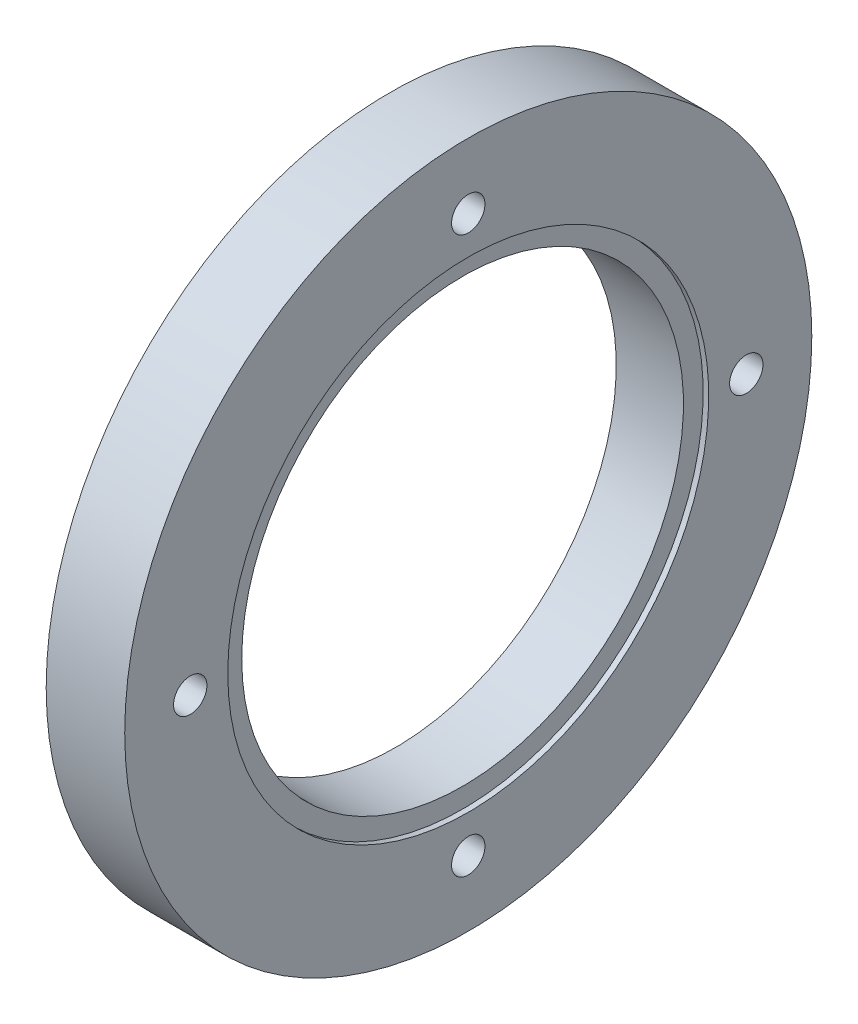
SolidWorks part; units mm, degrees
ref_plane "Front Plane" through (0, 0, 0) normal (0, 0, 1) x (1, 0, 0)
ref_plane "Top Plane" through (0, 0, 0) normal (0, 1, 0) x (1, 0, 0)
ref_plane "Right Plane" through (0, 0, 0) normal (1, 0, 0) x (0, 0, -1)
sketch "Sketch1" plane through (0, 0, 0) normal (0, 0, 1) x (1, 0, 0)
  line L0 (-801.9206, 0) -> (36107.5283, 0) construction
  line L10 (17.6402, 24.5) -> (17.6402, 35)
  line L12 (17.6402, 35) -> (9.6402, 35)
  line L16 (17.6402, 24.5) -> (17.0742, 24.5)
  line L17 (17.0742, 24.5) -> (17.0625, 22.5)
  line L18 (9.6402, 35) -> (9.6402, 24.5)
  line L22 (15.0625, 22.5) -> (17.0625, 22.5)
  line L28 (9.6402, 24.5) -> (10.2062, 24.5)
  line L29 (10.2062, 24.5) -> (10.2179, 22.5)
  line L30 (10.2179, 22.5) -> (15.0625, 22.5)
  point P1 (0, 0)
  dimension "D1" = 8
  dimension "D5" = 35
  dimension "D3" = 0.566
  dimension "D8" = 24.5
  dimension "D9" = 2
  dimension "D10" = 2
revolve "Revolve17" add sketch "Sketch1" angle 360 about L0
sketch "Sketch4" plane through (9.6402, 0, 0) normal (-1, 0, 0) x (0, 0, 1)
  circle A0 centre (0, 0) radius 28.325 construction
  point P3 (0, 28.325)
  point P7 (28.325, 0)
  point P12 (-28.325, 0)
  point P13 (0, -28.325)
  dimension "D1" = 56.65
hole_wizard "M3 Clearance Hole1" positions "Sketch4" profile "Sketch5" hole size "M3" standard "ISO"
sketch "Sketch5" plane through (9.6402, -28.325, 0) normal (0, 1, 0) x (0, 0, 1)
  line L0 (0, 0) -> (0, 9.0215)
  line L1 (0, 9.0215) -> (1.7, 8)
  line L2 (1.7, 8) -> (1.7, 0)
  line L5 (1.7, 0) -> (0, 0)
  line L10 (0, 9.0215) -> (-1.7, 8) construction
  line L11 (0, -6.35) -> (0, 107.95) construction
  dimension "Hole Dia." = 3.4
  dimension "Hole Depth" = 8
  dimension "Drill Angle" = 118
